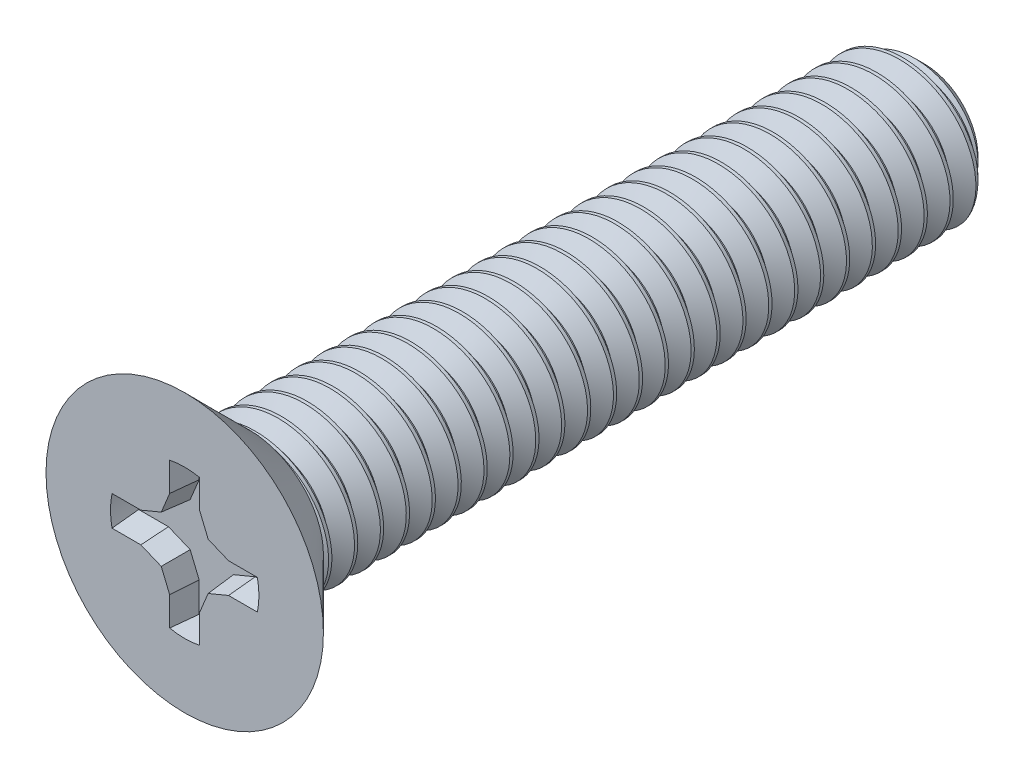
SolidWorks part; units mm, degrees
note: '?' marks a value the reader was unsure of.
material "Chrome Stainless Steel"
ref_plane "Front Plane" through (0, 0, 0) normal (0, 0, 1) x (1, 0, 0)
ref_plane "Top Plane" through (0, 0, 0) normal (0, 1, 0) x (1, 0, 0)
ref_plane "Right Plane" through (0, 0, 0) normal (1, 0, 0) x (0, 0, -1)
ref_axis "CentralAxis" through (0, 0, -19.0886) along (0, 0, 1)?
sketch "Sketch1" plane through (0, 0, 0) normal (1, 0, 0) x (0, 0, -1)
  line L0 (0, 0) -> (-2.2, 0) construction
  line L1 (-2.2, 3.75) -> (-2.2, -3.75) construction
  line L2 (-2.2, 3.75) -> (0, 1.55) construction
  line L3 (-2.2, -3.75) -> (0, -1.55) construction
  line L4 (0, 2) -> (0, -2) construction
  line L5 (0, 0) -> (17.8, 0) construction
  line L6 (0, 2) -> (0.7, 2) construction
  line L7 (0, 2) -> (-0.45, 2) construction
  line L8 (17.8, 1.55) -> (17.8, -1.55) construction
  point P6 (-2.2, 0)
  point P11 (0, 0)
  point P16 (-0.45, 2)
  point P17 (15.35, -2)
  point P20 (17.8, 0)
  point P21 (-1.1, 0)
  point P22 (15.35, -1.55)
  point P23 (17.8, -1.55)
  point P25 (17.8, 1.55)
  dimension "Head Height" = 2.2
  dimension "Head Diameter" = 7.5
  dimension "Countersink Angle" = 90
  dimension "Thread OD" = 4
  dimension "Length" = 20
  dimension "Thread Pitch" = 0.7
  dimension "D1" = 2.45
sketch "Sketch2" plane through (0, 0, 0) normal (0, 0, 1) x (1, 0, 0)
  line L0 (0.4064, 2.0066) -> (-0.4064, 2.0066) construction
  circle A0 centre (0, 0) radius 2.0066 construction
  point P3 (0, 2.0066)
  point P7 (0, 2.0066)
  dimension "Drive Dia" = 4.0132
  dimension "Drive Width" = 0.8128
sketch "Sketch3" plane through (0, 0, 0) normal (1, 0, 0) x (0, 0, -1)
  line L0 (-2.2, 0) -> (-2.2, 3.75)
  line L1 (-2.2, 3.75) -> (-0.45, 2)
  line L2 (-2.2, 3.75) -> (0, 1.55) construction
  line L3 (0, 2) -> (0.7, 2) construction
  line L4 (-2.2, 0) -> (-0.45, 0)
  line L5 (0, 0) -> (-2.2, 0) construction
  line L6 (-0.45, 0) -> (-0.45, 2)
revolve "Revolve1" add sketch "Sketch3" angle 360 about L4
sketch "Sketch5" plane through (0, 0, 0) normal (1, 0, 0) x (0, 0, -1)
  line L0 (17.8, 0) -> (-0.45, 0)
  line L1 (0, 0) -> (17.8, 0) construction
  line L2 (-0.45, 0) -> (-0.45, 2)
  line L3 (-0.45, 2) -> (17.247, 2)
  line L4 (17.247, 2) -> (17.8, 1.447)
  line L5 (17.8, 1.447) -> (17.8, 0)
  line L6 (17.247, 2) -> (17.8, 2) construction
  line L7 (17.8, 2) -> (17.8, 1.447) construction
  line L8 (0, 2) -> (0.7, 2) construction
  line L9 (-0.45, -2) -> (-0.45, 2) construction
  dimension "D1" = 0.553
revolve "Revolve2" add sketch "Sketch5" angle 360 about L0
sketch "Sketch4" plane through (0, 0, 2.2) normal (0, 0, 1) x (1, 0, 0)
  line L0 (0, 0) -> (0, 2.0066)
  line L1 (0, 0) -> (2.0066, 0)
  line L2 (0, 0) -> (1.1857, 1.1857) construction
  line L3 (0.4064, 1.965) -> (0.4064, 1.1857)
  line L4 (0.4064, 1.1857) -> (0.4064, 0.4064) construction
  line L5 (1.1857, 0.4064) -> (0.4064, 0.4064) construction
  line L6 (1.965, 0.4064) -> (1.1857, 0.4064)
  line L7 (0.4064, 1.1857) -> (0.6347, 0.6347)
  line L8 (0.6347, 0.6347) -> (1.1857, 0.4064)
  line L9 (0, 2.0066) -> (0, 3.75) construction
  line L10 (0, 3.75) -> (0, -3.75) construction
  circle A0 centre (0, 0) radius 2.0066 construction
  arc A1 (0, 2.0066) -> (0.4064, 1.965) centre (0, 0) cw
  arc A2 (2.0066, 0) -> (1.965, 0.4064) centre (0, 0) ccw
  arc A3 (1.1857, 0.4064) -> (0.4064, 1.1857) centre (1.1857, 1.1857) cw construction
  circle A4 centre (0, 0) radius 3.75 construction
  point P8 (0.6347, 0.6347)
  point P22 (0, -2.0066)
  point P23 (0, 2.0066)
  dimension "D1" = 1.7434
extrude "Cut-Extrude1" cut sketch "Sketch4" against normal blind 0.7333 contours L1 A2 L6 L8 L7 L3 A1 L0
pattern_circular "CirPattern1" count 4 over 360 about axis through (0, 0, 0) along (0, 0, 1) of "Cut-Extrude1"
draft "Draft2" type of draft neutral plane draft angle 5 faces to draft 16 face at (-1.5754, 0.4064, 1.8333) face at (-0.9102, 0.5205, 1.8333) face at (-0.5205, 0.9102, 1.8333) face at (-0.4064, 1.5754, 1.8333) face at (0.4064, 1.5754, 1.8333) face at (0.5205, 0.9102, 1.8333) face at (0.9102, 0.5205, 1.8333) face at (1.5754, 0.4064, 1.8333) face at (1.5754, -0.4064, 1.8333) face at (0.9102, -0.5205, 1.8333) face at (0.5205, -0.9102, 1.8333) face at (0.4064, -1.5754, 1.8333) face at (-0.4064, -1.5754, 1.8333) face at (-0.5205, -0.9102, 1.8333) face at (-0.9102, -0.5205, 1.8333) face at (-1.5754, -0.4064, 1.8333) neutral plane through (0, 0, 2.2) neutral plane normal (0, 0, 1) parameters "D1"=5
ref_plane "Plane1" through (0, 0, 0.45) normal (0, 0, -1) x (-1, 0, 0)
split "Split1" trim tools "Plane1" bodies to split 107 105 resulting bodies 108 109
sketch "Sketch6" plane through (0, 0, -17.8) normal (0, 0, 1) x (1, 0, 0)
  circle A1 centre (0, 0) radius 2
  circle A2 centre (0, 0) radius 2
  dimension "D1" = 0
curve "Helix/Spiral1" pitch 0.7 height 20 turns 28.5714
sketch "Sketch7" plane through (0, 0, 0) normal (1, 0, 0) x (0, 0, -1)
  line L0 (17.7563, 2.0758) -> (18.4563, 2.0758) construction
  line L1 (17.7563, 2.0758) -> (18.1062, 1.4696) construction
  line L2 (18.1062, 1.4696) -> (18.4563, 2.0758) construction
  line L3 (18.0625, 1.5453) -> (18.15, 1.5453) construction
  line L4 (17.8, 2) -> (18.4125, 2) construction
  line L5 (18.1062, 2) -> (18.1062, 2.0758) construction
  line L6 (18.1062, 1.5453) -> (18.1062, 1.4696) construction
  line L7 (18.1063, 2.0379) -> (17.7781, 2.0379) construction
  line L10 (18.15, 1.5453) -> (18.0625, 1.5453)
  line L11 (17.7781, 2.0379) -> (18.0625, 1.5453)
  line L12 (17.7781, 2.0379) -> (18.4344, 2.0379)
  line L13 (18.4344, 2.0379) -> (18.15, 1.5453)
  dimension "D1" = 0.7
  dimension "D2" = 0.0875
sweep "Cut-Sweep1" cut profiles "Sketch7" path "Helix/Spiral1"
combine bodies "Combine1" operation type add bodies to combine 109 110
ref_plane "Plane2" through (0, 0, 0.45) normal (0, 0, 1) x (1, 0, 0)
sketch "Sketch8" plane through (0, 0, 0.45) normal (0, 0, 1) x (1, 0, 0)
  circle A0 centre (0, 0) radius 2
extrude "Boss-Extrude1" add sketch "Sketch8" against normal up to vertex (0.45 mm away) draft 45 up to point (0, 1.55, 0)
equation "\"D1@Sketch5\" = \"Thread Pitch@Sketch1\" * .79"
equation "\"D4@Helix/Spiral1\" = \"Thread Pitch@Sketch1\""
equation "\"D3@Helix/Spiral1\"=\"Length@Sketch1\""
equation "\"D1@Sketch7\" = \"Thread Pitch@Sketch1\""
equation "\"D2@Sketch7\" = \"Thread Pitch@Sketch1\" / 8"
equation "\"D1@Sketch1\"=\"Thread Pitch@Sketch1\"*3.5"
equation "\"D1@Cut-Extrude1\"=\"Head Height@Sketch1\"/3"
